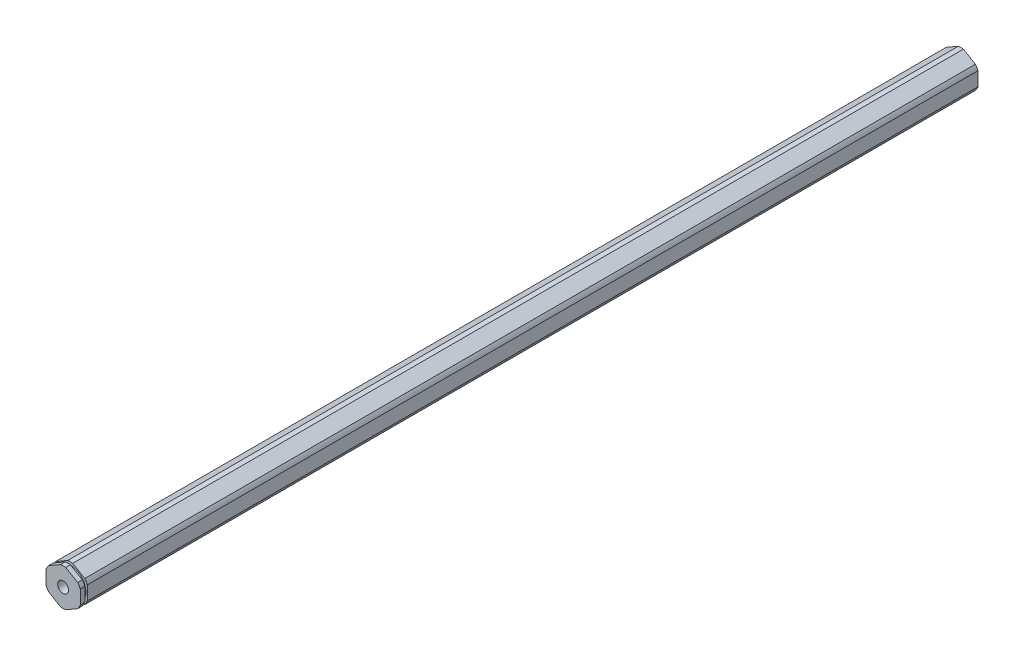
SolidWorks part; units mm, degrees
ref_plane "Front Plane" through (0, 0, 0) normal (0, 0, 1) x (1, 0, 0)
ref_plane "Top Plane" through (0, 0, 0) normal (0, 1, 0) x (1, 0, 0)
ref_plane "Right Plane" through (0, 0, 0) normal (1, 0, 0) x (0, 0, -1)
sketch "Sketch1" plane through (0, 0, 0) normal (0, 0, 1) x (1, 0, 0)
  line L1 (0, 7.3323) -> (-6.35, 3.6662)
  line L2 (-6.35, 3.6662) -> (-6.35, -3.6662)
  line L3 (-6.35, -3.6662) -> (0, -7.3323)
  line L4 (0, -7.3323) -> (6.35, -3.6662)
  line L5 (6.35, -3.6662) -> (6.35, 3.6662)
  line L6 (6.35, 3.6662) -> (0, 7.3323)
  circle A0 centre (0, 0) radius 6.35 construction
  circle A1 centre (0, 0) radius 6.858
  dimension "D1" = 12.7
  dimension "D2" = 13.716
extrude "Boss-Extrude1" add sketch "Sketch1" along normal mid plane 332.8035 contours L5 A1 L6 L1 L2 L3 L4 region at (0, 0, 0)
hole_wizard "#10-32 Tapped Hole1" positions "3DSketch1" profile "Sketch2" tap size "#10-32" standard "ANSI Inch"
sketch3d "3DSketch1"
  line L0 (0, 0, 166.4017) -> (0, 0, -166.4017) construction
  line L1 (0, 0, 166.4017) -> (0, 0, -166.4017) construction
  point P0 (0, 0, 166.4017)
  point P4 (0, 0, -166.4017)
sketch "Sketch2" plane through (0, 0, 166.4017) normal (1, 0, 0) x (0, -1, 0)
  line L0 (0, 0) -> (0, 17.5608)
  line L1 (0, 17.5608) -> (2.0193, 16.3474)
  line L2 (2.0193, 16.3474) -> (2.0193, 0)
  line L5 (2.0193, 0) -> (0, 0)
  line L10 (0, 17.5608) -> (-2.0193, 16.3474) construction
  line L11 (0, -6.35) -> (0, 107.95) construction
  dimension "Tap Drill Dia." = 4.0386
  dimension "Tap Drill Depth" = 16.3474
  dimension "Drill Angle" = 118
cosmetic thread "Hole Thread1" parameters "D1"=13.97, "D2"=4.826
cosmetic thread "Hole Thread2" parameters "D1"=13.97, "D2"=4.826
sketch "Sketch5" plane through (0, 0, 0) normal (1, 0, 0) x (0, 0, -1)
  line L0 (166.4017, 6.858) -> (-166.4017, 6.858) construction
  line L1 (-164.6872, 6.858) -> (-163.7982, 6.858)
  line L2 (-164.6872, 6.858) -> (-164.6872, 5.8547)
  line L3 (-164.6872, 5.8547) -> (-163.7982, 5.8547)
  line L4 (-163.7982, 6.858) -> (-163.7982, 5.8547)
  line L5 (-165.0472, 0) -> (-158.8423, 0) construction
  dimension "D1" = 5.8547
  dimension "D2" = 0.889
  dimension "D3" = 1.7145
revolve "Cut-Revolve1" cut sketch "Sketch5" angle 360 about L5
mirror "Mirror1" [suppressed] about plane through (0, 0, 0) normal (0, 0, 1)
